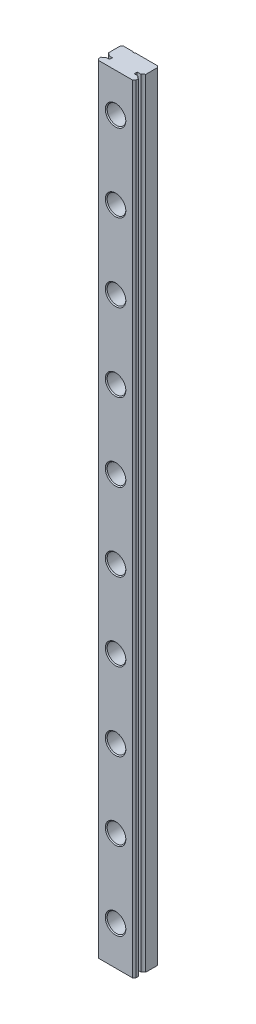
SolidWorks part; units mm, degrees
ref_plane "Horní rovina" through (0, 0, 0) normal (0, 0, 1) x (1, 0, 0)
ref_plane "Přední rovina" through (0, 0, 0) normal (0, 1, 0) x (1, 0, 0)
ref_plane "Pravá rovina" through (0, 0, 0) normal (1, 0, 0) x (0, 0, -1)
sketch "Skica1" plane through (0, 0, 0) normal (0, 1, 0) x (1, 0, 0)
  line L0 (-5.5, -8) -> (5.5, -8)
  line L2 (6, -7.5) -> (6, -6.6619)
  line L3 (5.2091, -6) -> (4, -5.95)
  line L4 (4, -5.95) -> (4, -5.05)
  line L5 (4, -5.05) -> (5.2091, -5)
  line L6 (6, -4.3381) -> (6, -0.5)
  line L8 (5.5, 0) -> (-1.6, 0)
  line L9 (-2.4, 0) -> (-5.5, 0)
  line L11 (-6, -0.5) -> (-6, -4.3381)
  line L12 (-5.2091, -5) -> (-4, -5.05)
  line L13 (-4, -5.05) -> (-4, -5.95)
  line L14 (-4, -5.95) -> (-5.2091, -6)
  line L15 (-6, -6.6619) -> (-6, -7.5)
  line L17 (0, -9.4784) -> (0, 1.3023) construction
  line L18 (5.5, -8) -> (6, -7.5)
  line L19 (-6, -7.5) -> (-5.5, -8)
  line L20 (-5.5, 0) -> (-6, -0.5)
  line L21 (6, -0.5) -> (5.5, 0)
  line L22 (4, -5.5) -> (-4, -5.5) construction
  arc A0 (5.2091, -6) -> (6, -6.6619) centre (6.3, -5.5) ccw
  arc A1 (6, -4.3381) -> (5.2091, -5) centre (6.3, -5.5) ccw
  arc A2 (-2.4, 0) -> (-1.6, 0) centre (-2, 0.3) ccw
  arc A5 (-6, -4.3381) -> (-5.2091, -5) centre (-6.3, -5.5) cw
  arc A6 (-5.2091, -6) -> (-6, -6.6619) centre (-6.3, -5.5) cw
  point P0 (-6, -8)
  point P1 (6, -8)
  point P14 (6, 0)
  point P19 (-6, 0)
  dimension "D4" = 1.2
  dimension "D18" = 0.5
  dimension "D1" = 6
  dimension "D3" = 8
  dimension "D5" = 6.3
  dimension "D6" = 5.5
  dimension "D7" = 4
  dimension "D8" = 4
  dimension "D13" = 0.9
  dimension "D14" = 0.9
  dimension "D15" = 5.5
  dimension "D16" = 1
  dimension "D17" = 0.5
  dimension "D19" = 2
  dimension "D20" = 0.3
  dimension "D9" = 0.5
  dimension "D10" = 0.5
  dimension "D11" = 0.5
  dimension "D12" = 0.5
  dimension "D21" = 0.5
  dimension "D22" = 0.5
  dimension "D23" = 0.5
  dimension "D24" = 0.5
  dimension "D25" = 6
extrude "Delka" add sketch "Skica1" along normal blind 250
hole_wizard "Díra1" positions "Skica3" profile "Skica4" legacy end condition through all
sketch "Skica3" plane through (0, 0, 8) normal (0, 0, 1) x (1, 0, 0)
  point P0 (0, 12.5)
  point P2 (0, 12.5)
  dimension "D1" = 12.5
sketch "Skica4" plane through (0, 12.5, 8) normal (1, 0, 0) x (0, -1, 0)
  line L0 (0, 0) -> (0, 8.1491)
  line L1 (0, 8.1491) -> (1.75, 8.1491)
  line L2 (1.75, 8.1491) -> (1.75, 4.5)
  line L3 (1.75, 4.5) -> (3, 4.5)
  line L4 (3, 4.5) -> (3, 0)
  line L5 (3, 0) -> (0, 0)
  line L6 (0, 110) -> (0, -10) construction
  dimension "Průměr" = 3.5
  dimension "Hloubka" = 8.1491
  dimension "Průměr válc. zahloubení" = 6
  dimension "Hloubka válc. zahloubení" = 4.5
chamfer "Zkosení1" distance 0.3 angle 45 2 edges at (1.75, 12.5, 0) (3, 12.5, 8)
pattern_linear "LinPole1" count 10 spacing 25 along (0, 1, 0) of "Díra1", "Zkosení1"
equation "\"D17@Skica1\"=\"D16@Skica1\"/2"
equation "\"D10@Skica1\"=\"D9@Skica1\""
equation "\"D11@Skica1\"=\"D9@Skica1\""
equation "\"D12@Skica1\"=\"D9@Skica1\""
equation "\"D21@Skica1\"=\"D9@Skica1\""
equation "\"D22@Skica1\"=\"D9@Skica1\""
equation "\"D23@Skica1\"=\"D9@Skica1\""
equation "\"D24@Skica1\"=\"D9@Skica1\""
equation "\"P\"= 25mm"
equation "\"Emin\"= 5mm"
equation "\"Emax\"= 20mm"
equation "\"Hc\"= round (  ( \"D1@Delka\" - 2 * \"Emin\" )  / \"P\" ) "
equation "\"E\"= ( \"L\" - ( ( \"Hc\" - 1 ) * \"P\" ) ) / 2"
equation "\"L\"= 250"
equation "\"D1@Delka\" = \"L\""
equation "\"D1@LinPole1\"= \"Hc\""
equation "\"D3@LinPole1\"= \"P\""
equation "\"D1@Skica3\"= \"E\""
equation "\"D25@Skica1\"=\"D1@Skica1\""
equation "\"Přidat vysunutím1\"= \"L\""
equation "\"Delka\"= \"L\""
